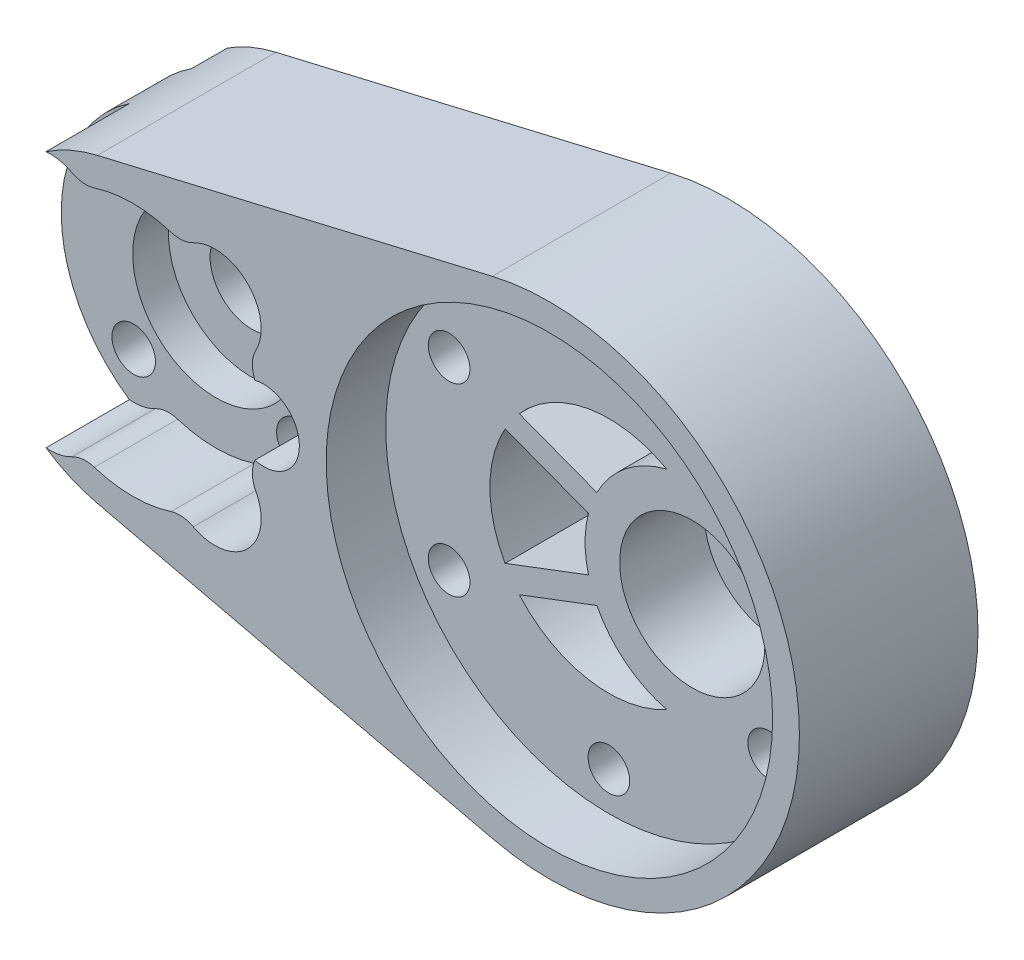
SolidWorks part; units mm, degrees
material "ABS"
ref_plane "Front Plane" through (0, 0, 0) normal (0, 0, 1) x (1, 0, 0)
ref_plane "Top Plane" through (0, 0, 0) normal (0, 1, 0) x (1, 0, 0)
ref_plane "Right Plane" through (0, 0, 0) normal (1, 0, 0) x (0, 0, -1)
sketch "layout" plane through (0, 0, 0) normal (0, 0, 1) x (1, 0, 0)
  line L0 (-87.1613, 0) -> (148.5806, 0) construction
  line L1 (0, 77.4516) -> (0, -79.4839) construction
  line L2 (-2.9714, 12.6559) -> (30.2, 20.4441)
  line L3 (30.2, -20.4441) -> (-2.9714, -12.6559)
  circle A0 centre (0, 0) radius 13
  circle A1 centre (35, 0) radius 21
  circle A3 centre (42, 0) radius 3
  circle A4 centre (11, 0) radius 1.5
  dimension "D1" = 7
  dimension "D2" = 42
  dimension "D3" = 26
  dimension "D4" = 42
  dimension "D5" = 6
  dimension "D6" = 31
  dimension "D7" = 3
sketch "Sketch2" plane through (0, 0, 0) normal (0, 0, 1) x (1, 0, 0)
  line L0 (-2.9714, 12.6559) -> (30.2, 20.4441)
  line L1 (30.2, -20.4441) -> (-2.9714, -12.6559)
  arc A0 (-2.9714, 12.6559) -> (-2.9714, -12.6559) centre (0, 0) ccw
  arc A1 (30.2, -20.4441) -> (30.2, 20.4441) centre (35, 0) ccw
extrude "Boss-Extrude1" add sketch "Sketch2" along normal blind 15
sketch "Sketch5" plane through (0, 0, 15) normal (0, 0, 1) x (1, 0, 0)
  line B0 (2.48, 1.6881) -> (2.48, -1.6881)
  line B1 (-16.002, 0.635) -> (-2.932, 0.635)
  line B2 (-16.002, 4.7625) -> (-16.002, 0.635)
  line B3 (-13.2056, 4.7625) -> (-16.002, 4.7625)
  line B4 (-12.573, -4.7625) -> (-12.573, -4.8306)
  line B5 (-16.002, -4.7625) -> (-12.573, -4.7625)
  line B6 (-16.002, -0.635) -> (-16.002, -4.7625)
  line B7 (-2.932, -0.635) -> (-16.002, -0.635)
  arc B8 (1.3492, -2.6795) -> (2.48, -1.6881) centre (1.48, -1.6881) ccw
  arc B9 (2.48, 1.6881) -> (1.3492, 2.6795) centre (1.48, 1.6881) ccw
  arc B10 (1.3492, 2.6795) -> (-2.932, 0.635) centre (0, 0) ccw
  arc B11 (-13.2056, 4.7625) -> (-10.2587, 7.3504) centre (-13.2056, 7.7343) ccw
  arc B12 (-5.329, 9.8908) -> (-10.2587, 7.3504) centre (-6.9148, 6.9148) ccw
  arc B13 (-5.329, 9.8908) -> (-3.0721, 9.6844) centre (-3.9553, 12.4687) ccw
  arc B14 (3.0721, 9.6844) -> (-3.0721, 9.6844) centre (0, 0) ccw
  arc B15 (3.0721, 9.6844) -> (5.329, 9.8908) centre (3.9553, 12.4687) ccw
  arc B16 (9.8908, 5.329) -> (5.329, 9.8908) centre (6.9148, 6.9148) ccw
  arc B17 (9.8908, 5.329) -> (9.6844, 3.0721) centre (12.4687, 3.9553) ccw
  arc B18 (9.6844, -3.0721) -> (9.6844, 3.0721) centre (0, 0) ccw
  arc B19 (9.6844, -3.0721) -> (9.8908, -5.329) centre (12.4687, -3.9553) ccw
  arc B20 (5.329, -9.8908) -> (9.8908, -5.329) centre (6.9148, -6.9148) ccw
  arc B21 (5.329, -9.8908) -> (3.0721, -9.6844) centre (3.9553, -12.4687) ccw
  arc B22 (-3.0721, -9.6844) -> (3.0721, -9.6844) centre (0, 0) ccw
  arc B23 (-3.0721, -9.6844) -> (-5.329, -9.8908) centre (-3.9553, -12.4687) ccw
  arc B24 (-10.2587, -7.3504) -> (-5.329, -9.8908) centre (-6.9148, -6.9148) ccw
  arc B25 (-10.2587, -7.3504) -> (-12.573, -4.8306) centre (-13.2056, -7.7343) ccw
  arc B26 (-2.932, -0.635) -> (1.3492, -2.6795) centre (0, 0) ccw
sketch_block_instance "Block1-1"
sketch_block "Block1"
sketch "Sketch6" plane through (0, 0, 15) normal (0, 0, 1) x (1, 0, 0)
  line L5 (6.9148, 6.9148) -> (-6.9148, 6.9148) construction
  line L6 (-6.9148, 6.9148) -> (-6.9148, -6.9148) construction
  line L7 (-6.9148, -6.9148) -> (6.9148, -6.9148) construction
  line L8 (6.9148, -6.9148) -> (6.9148, 6.9148) construction
  circle A0 centre (0, 0) radius 3.5
  circle A2 centre (0, 0) radius 9.779 construction
  circle A3 centre (-6.9148, 6.9148) radius 1.8288
  circle A4 centre (6.9148, 6.9148) radius 1.8288
  circle A5 centre (6.9148, -6.9148) radius 1.8288
  circle A6 centre (-6.9148, -6.9148) radius 1.8288
  dimension "D1" = 3.6576
  dimension "D2" = 19.558
  dimension "D3" = 7
extrude "hub mount hole pattern" cut sketch "Sketch6" against normal through all
sketch "Sketch7" plane through (0, 0, 15) normal (0, 0, 1) x (1, 0, 0)
  line L1 (21.5766, 7.75) -> (21.5766, -7.75) construction
  line L2 (21.5766, -7.75) -> (35, -15.5) construction
  line L3 (35, -15.5) -> (48.4234, -7.75) construction
  line L4 (48.4234, -7.75) -> (48.4234, 7.75) construction
  line L5 (48.4234, 7.75) -> (35, 15.5) construction
  line L6 (35, 15.5) -> (21.5766, 7.75) construction
  circle A0 centre (35, 0) radius 15.5 construction
  circle A1 centre (21.5766, 7.75) radius 1.75
  circle A2 centre (35, 15.5) radius 1.75
  circle A3 centre (48.4234, 7.75) radius 1.75
  circle A4 centre (48.4234, -7.75) radius 1.75
  circle A5 centre (35, -15.5) radius 1.75
  circle A6 centre (21.5766, -7.75) radius 1.75
  circle A7 centre (42, 0) radius 3.25
  dimension "D1" = 3.5
  dimension "D2" = 6.5
  dimension "D3" = 31
extrude "motor hole pattern" cut sketch "Sketch7" against normal through all
sketch "Sketch8" plane through (0, 0, 15) normal (0, 0, 1) x (1, 0, 0)
  circle A0 centre (35, 0) radius 18.75
  dimension "D1" = 37.5
extrude "motor cutout" cut sketch "Sketch8" against normal blind 5
sketch "Sketch9" plane through (0, 0, 15) normal (0, 0, 1) x (1, 0, 0)
  arc A0 (-7.2811, 10.7696) -> (-7.2811, -10.7696) centre (0, 0) ccw
  arc A156 (-10.7546, -7.415) -> (-5.0938, -10.3321) centre (-6.9148, -6.9148) ccw
  arc A157 (-3.2233, -10.161) -> (-5.0938, -10.3321) centre (-3.9553, -12.4687) ccw
  arc A158 (-3.2233, -10.161) -> (3.2233, -10.161) centre (0, 0) ccw
  arc A159 (5.0938, -10.3321) -> (3.2233, -10.161) centre (3.9553, -12.4687) ccw
  arc A160 (10.161, -3.2233) -> (10.3321, -5.0938) centre (12.4687, -3.9553) ccw
  arc A161 (5.0938, -10.3321) -> (10.3321, -5.0938) centre (6.9148, -6.9148) ccw
  arc A162 (10.161, -3.2233) -> (10.161, 3.2233) centre (0, 0) ccw
  arc A163 (10.3321, 5.0938) -> (10.161, 3.2233) centre (12.4687, 3.9553) ccw
  arc A164 (10.3321, 5.0938) -> (5.0938, 10.3321) centre (6.9148, 6.9148) ccw
  arc A165 (3.2233, 10.161) -> (5.0938, 10.3321) centre (3.9553, 12.4687) ccw
  arc A166 (-5.0938, 10.3321) -> (-10.7546, 7.415) centre (-6.9148, 6.9148) ccw
  arc A167 (-5.0938, 10.3321) -> (-3.2233, 10.161) centre (-3.9553, 12.4687) ccw
  arc A168 (3.2233, 10.161) -> (-3.2233, 10.161) centre (0, 0) ccw
  arc A169 (-7.2811, -10.7696) -> (-5.0938, -10.3321) centre (-6.9148, -6.9148) ccw
  arc A170 (-3.2233, -10.161) -> (-5.0938, -10.3321) centre (-3.9553, -12.4687) ccw
  arc A171 (-3.2233, -10.161) -> (3.2233, -10.161) centre (0, 0) ccw
  arc A172 (5.0938, -10.3321) -> (3.2233, -10.161) centre (3.9553, -12.4687) ccw
  arc A173 (10.161, -3.2233) -> (10.3321, -5.0938) centre (12.4687, -3.9553) ccw
  arc A174 (5.0938, -10.3321) -> (10.3321, -5.0938) centre (6.9148, -6.9148) ccw
  arc A175 (10.161, -3.2233) -> (10.161, 3.2233) centre (0, 0) ccw
  arc A176 (10.3321, 5.0938) -> (10.161, 3.2233) centre (12.4687, 3.9553) ccw
  arc A177 (10.3321, 5.0938) -> (5.0938, 10.3321) centre (6.9148, 6.9148) ccw
  arc A178 (3.2233, 10.161) -> (5.0938, 10.3321) centre (3.9553, 12.4687) ccw
  arc A179 (-5.0938, 10.3321) -> (-7.2811, 10.7696) centre (-6.9148, 6.9148) ccw
  arc A180 (-5.0938, 10.3321) -> (-3.2233, 10.161) centre (-3.9553, 12.4687) ccw
  arc A181 (3.2233, 10.161) -> (-3.2233, 10.161) centre (0, 0) ccw
  dimension "D1" = 0.5
extrude "hub mount cutout" cut sketch "Sketch9" against normal blind 7
sketch "Sketch10" plane through (0, 0, 0) normal (0, 0, -1) x (-1, 0, 0)
  circle A0 centre (-11, 0) radius 5
  dimension "D1" = 10
extrude "Boss-Extrude2" add sketch "Sketch10" along normal blind 5.5
sketch "Sketch12" plane through (0, 0, 0) normal (0, 0, 1) x (1, 0, 0)
  circle A0 centre (11, 0) radius 1.55
  dimension "D1" = 3.1
extrude "Linkage pin hole" cut sketch "Sketch12" against normal through all both and the other way through all
chamfer "Chamfer1" distance 2.75 angle 45 1 edges at (6, 0, -5.5)
sketch "Sketch13" plane through (0, 0, 10) normal (0, 0, 1) x (1, 0, 0)
  circle A0 centre (42, 0) radius 6.1
  dimension "D1" = 12.2
extrude "Cut-Extrude7" cut sketch "Sketch13" against normal blind 7.1
sketch "Sketch14" plane through (0, 0, 8) normal (0, 0, 1) x (1, 0, 0)
  circle A0 centre (0, 0) radius 7
  dimension "D1" = 14
extrude "Cut-Extrude8" cut sketch "Sketch14" against normal blind 3
sketch "Sketch15" plane through (0, 0, 0) normal (0, 0, -1) x (-1, 0, 0)
  circle A0 centre (-21.5766, -7.75) radius 3.5
  circle A1 centre (-35, -15.5) radius 3.5
  circle A2 centre (-48.4234, -7.75) radius 3.5
  circle A3 centre (-48.4234, 7.75) radius 3.5
  circle A4 centre (-35, 15.5) radius 3.5
  circle A5 centre (-21.5766, 7.75) radius 3.5
  dimension "D1" = 7
extrude "Cut-Extrude9" cut sketch "Sketch15" against normal offset from surface (5 mm away) 5 up to face at (48.1, 0, 10)
sketch "Sketch16" plane through (0, 0, 8) normal (0, 0, 1) x (1, 0, 0)
  circle A0 centre (11, 0) radius 3
  dimension "D1" = 6
extrude "Cut-Extrude10" cut sketch "Sketch16" against normal offset from surface 10.5 and the other way through all up to face at (8.75, 0, -5.5)
sketch "Sketch17" plane through (0, 0, 10) normal (0, 0, 1) x (1, 0, 0)
  arc A0 (39.8571, 8.7412) -> (39.8571, -8.7412) centre (35, 0) ccw
  arc A1 (39.8571, 8.7412) -> (39.8571, -8.7412) centre (42, 0) ccw
  dimension "D1" = 9
  dimension "D2" = 10
extrude "Cut-Extrude12" cut sketch "Sketch17" against normal offset from surface (7 mm away) 3 up to face at (18.0766, 7.75, 0)
sketch "Sketch18" plane through (0, 0, 10) normal (0, 0, 1) x (1, 0, 0)
  line L0 (21.5766, -7.75) -> (42, 0) construction
  line L1 (21.5766, 7.75) -> (42, 0) construction
  line L2 (27.472, -6.5825) -> (33.9923, -4.1082)
  line L3 (27.472, 6.5825) -> (33.9923, 4.1082)
  line L4 (26.2803, -4.8955) -> (33.2828, -2.2383)
  line L5 (26.2803, 4.8955) -> (33.2828, 2.2383)
  line L6 (21.9314, -8.6849) -> (44.8186, 0) construction
  line L7 (21.2218, -6.8151) -> (39.1814, 0) construction
  line L8 (21.9314, 8.6849) -> (44.8186, 0) construction
  line L9 (21.2218, 6.8151) -> (39.1814, 0) construction
  arc A0 (39.8571, 8.7412) -> (39.8571, -8.7412) centre (35, 0) ccw construction
  arc A1 (39.8571, 8.7412) -> (39.8571, -8.7412) centre (42, 0) ccw construction
  arc A2 (27.472, 6.5825) -> (26.2803, 4.8955) centre (35, 0) ccw
  arc A3 (33.9923, 4.1082) -> (33.2828, 2.2383) centre (42, 0) ccw
  arc A5 (26.2803, -4.8955) -> (27.472, -6.5825) centre (35, 0) ccw
  arc A6 (33.2828, -2.2383) -> (33.9923, -4.1082) centre (42, 0) ccw
  dimension "D1" = 1
  dimension "D2" = 1
extrude "Boss-Extrude3" add sketch "Sketch18" against normal up to next
sketch "Sketch19" plane through (0, 0, 0) normal (0, 0, -1) x (-1, 0, 0)
  circle A0 centre (-6.9148, -6.9148) radius 4
  circle A1 centre (-6.9148, 6.9148) radius 4
  circle A2 centre (6.9148, 6.9148) radius 4
  circle A3 centre (6.9148, -6.9148) radius 4
  dimension "D1" = 8
extrude "Cut-Extrude13" cut sketch "Sketch19" against normal offset from surface 5 and the other way through all up to face at (2.6581, 0, 8)
fillet "Fillet1" radius 5 2 edges at (16, 0, 0) (6, 0, 0)
